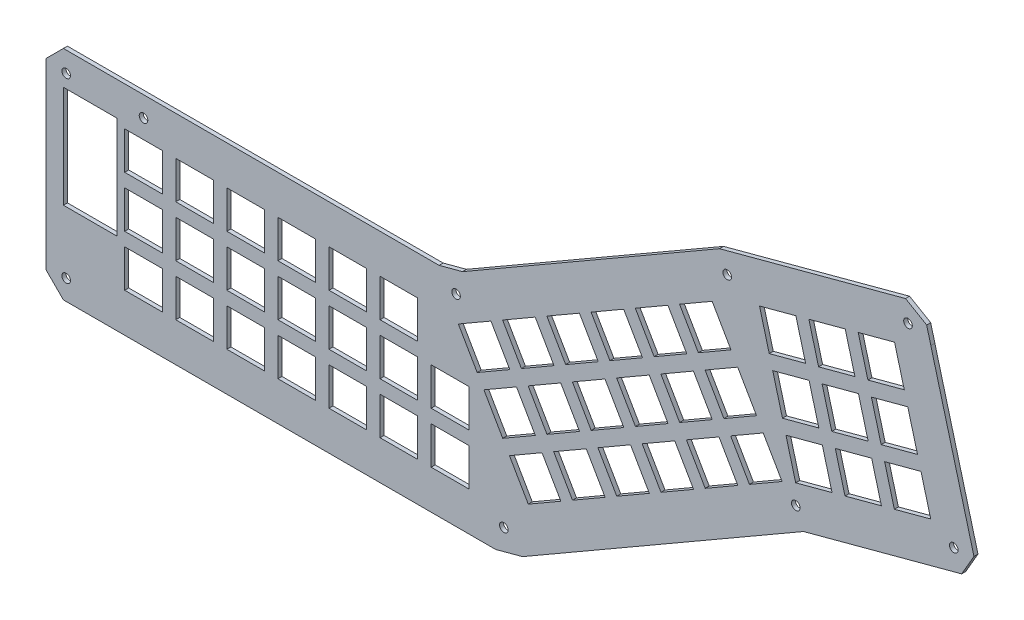
SolidWorks part; units mm, degrees
ref_plane "Plan de face" through (0, 0, 0) normal (0, 0, 1) x (1, 0, 0)
ref_plane "Plan de dessus" through (0, 0, 0) normal (0, 1, 0) x (1, 0, 0)
ref_plane "Plan de droite" through (0, 0, 0) normal (1, 0, 0) x (0, 0, -1)
sketch "Esquisse1" plane through (0, 0, 0) normal (0, 0, 1) x (1, 0, 0)
  line L0 (-73.9886, 18.0851) -> (-59.9886, 18.0851)
  line L1 (-73.9886, 37.0851) -> (-59.9886, 37.0851)
  line L2 (-73.9886, 37.0851) -> (-73.9886, 23.0851)
  line L3 (-73.9886, 23.0851) -> (-59.9886, 23.0851)
  line L4 (-59.9886, 37.0851) -> (-59.9886, 23.0851)
  line L5 (-73.9886, 18.0851) -> (-73.9886, 4.0851)
  line L6 (-73.9886, 4.0851) -> (-59.9886, 4.0851)
  line L7 (-59.9886, 18.0851) -> (-59.9886, 4.0851)
  line L8 (-73.9886, -0.9149) -> (-59.9886, -0.9149)
  line L9 (-73.9886, -0.9149) -> (-73.9886, -14.9149)
  line L10 (-73.9886, -14.9149) -> (-59.9886, -14.9149)
  line L11 (-59.9886, -0.9149) -> (-59.9886, -14.9149)
  line L12 (-73.9886, 37.0851) -> (-73.9886, 18.0851) construction
  line L13 (-54.9886, 18.0851) -> (-40.9886, 18.0851)
  line L14 (-54.9886, 37.0851) -> (-40.9886, 37.0851)
  line L15 (-54.9886, 37.0851) -> (-54.9886, 23.0851)
  line L16 (-54.9886, 23.0851) -> (-40.9886, 23.0851)
  line L17 (-40.9886, 37.0851) -> (-40.9886, 23.0851)
  line L18 (-54.9886, 18.0851) -> (-54.9886, 4.0851)
  line L19 (-54.9886, 4.0851) -> (-40.9886, 4.0851)
  line L20 (-40.9886, 18.0851) -> (-40.9886, 4.0851)
  line L21 (-54.9886, -0.9149) -> (-40.9886, -0.9149)
  line L22 (-54.9886, -0.9149) -> (-54.9886, -14.9149)
  line L23 (-54.9886, -14.9149) -> (-40.9886, -14.9149)
  line L24 (-40.9886, -0.9149) -> (-40.9886, -14.9149)
  line L25 (-54.9886, 37.0851) -> (-54.9886, 18.0851) construction
  line L26 (-35.9886, 18.0851) -> (-21.9886, 18.0851)
  line L27 (-35.9886, 37.0851) -> (-21.9886, 37.0851)
  line L28 (-35.9886, 37.0851) -> (-35.9886, 23.0851)
  line L29 (-35.9886, 23.0851) -> (-21.9886, 23.0851)
  line L30 (-21.9886, 37.0851) -> (-21.9886, 23.0851)
  line L31 (-35.9886, 18.0851) -> (-35.9886, 4.0851)
  line L32 (-35.9886, 4.0851) -> (-21.9886, 4.0851)
  line L33 (-21.9886, 18.0851) -> (-21.9886, 4.0851)
  line L34 (-35.9886, -0.9149) -> (-21.9886, -0.9149)
  line L35 (-35.9886, -0.9149) -> (-35.9886, -14.9149)
  line L36 (-35.9886, -14.9149) -> (-21.9886, -14.9149)
  line L37 (-21.9886, -0.9149) -> (-21.9886, -14.9149)
  line L38 (-35.9886, 37.0851) -> (-35.9886, 18.0851) construction
  line L39 (-16.9886, 18.0851) -> (-2.9886, 18.0851)
  line L40 (-16.9886, 37.0851) -> (-2.9886, 37.0851)
  line L41 (-16.9886, 37.0851) -> (-16.9886, 23.0851)
  line L42 (-16.9886, 23.0851) -> (-2.9886, 23.0851)
  line L43 (-2.9886, 37.0851) -> (-2.9886, 23.0851)
  line L44 (-16.9886, 18.0851) -> (-16.9886, 4.0851)
  line L45 (-16.9886, 4.0851) -> (-2.9886, 4.0851)
  line L46 (-2.9886, 18.0851) -> (-2.9886, 4.0851)
  line L47 (-16.9886, -0.9149) -> (-2.9886, -0.9149)
  line L48 (-16.9886, -0.9149) -> (-16.9886, -14.9149)
  line L49 (-16.9886, -14.9149) -> (-2.9886, -14.9149)
  line L50 (-2.9886, -0.9149) -> (-2.9886, -14.9149)
  line L51 (-16.9886, 37.0851) -> (-16.9886, 18.0851) construction
  line L52 (2.0114, 18.0851) -> (16.0114, 18.0851)
  line L53 (2.0114, 37.0851) -> (16.0114, 37.0851)
  line L54 (2.0114, 37.0851) -> (2.0114, 23.0851)
  line L55 (2.0114, 23.0851) -> (16.0114, 23.0851)
  line L56 (16.0114, 37.0851) -> (16.0114, 23.0851)
  line L57 (2.0114, 18.0851) -> (2.0114, 4.0851)
  line L58 (2.0114, 4.0851) -> (16.0114, 4.0851)
  line L59 (16.0114, 18.0851) -> (16.0114, 4.0851)
  line L60 (2.0114, -0.9149) -> (16.0114, -0.9149)
  line L61 (2.0114, -0.9149) -> (2.0114, -14.9149)
  line L62 (2.0114, -14.9149) -> (16.0114, -14.9149)
  line L63 (16.0114, -0.9149) -> (16.0114, -14.9149)
  line L64 (2.0114, 37.0851) -> (2.0114, 18.0851) construction
  line L65 (21.0114, 18.0851) -> (35.0114, 18.0851)
  line L66 (21.0114, 37.0851) -> (35.0114, 37.0851)
  line L67 (21.0114, 37.0851) -> (21.0114, 23.0851)
  line L68 (21.0114, 23.0851) -> (35.0114, 23.0851)
  line L69 (35.0114, 37.0851) -> (35.0114, 23.0851)
  line L70 (21.0114, 18.0851) -> (21.0114, 4.0851)
  line L71 (21.0114, 4.0851) -> (35.0114, 4.0851)
  line L72 (35.0114, 18.0851) -> (35.0114, 4.0851)
  line L73 (21.0114, -0.9149) -> (35.0114, -0.9149)
  line L74 (21.0114, -0.9149) -> (21.0114, -14.9149)
  line L75 (21.0114, -14.9149) -> (35.0114, -14.9149)
  line L76 (35.0114, -0.9149) -> (35.0114, -14.9149)
  line L77 (21.0114, 37.0851) -> (21.0114, 18.0851) construction
  line L78 (40.0114, 18.0851) -> (54.0114, 18.0851)
  line L79 (40.0114, 37.0851) -> (54.0114, 37.0851) construction
  line L80 (40.0114, 37.0851) -> (40.0114, 23.0851) construction
  line L81 (40.0114, 23.0851) -> (54.0114, 23.0851) construction
  line L82 (54.0114, 37.0851) -> (54.0114, 23.0851) construction
  line L83 (40.0114, 18.0851) -> (40.0114, 4.0851)
  line L84 (40.0114, 4.0851) -> (54.0114, 4.0851)
  line L85 (54.0114, 18.0851) -> (54.0114, 4.0851)
  line L86 (40.0114, -0.9149) -> (54.0114, -0.9149)
  line L87 (40.0114, -0.9149) -> (40.0114, -14.9149)
  line L88 (40.0114, -14.9149) -> (54.0114, -14.9149)
  line L89 (54.0114, -0.9149) -> (54.0114, -14.9149)
  line L90 (40.0114, 37.0851) -> (40.0114, 18.0851) construction
  line L91 (-73.9886, 18.0851) -> (-54.9886, 18.0851) construction
  line L92 (56.0114, 20.0851) -> (56.7532, 18.8002) construction
  line L93 (38.0114, 39.0851) -> (56.0114, 39.0851) construction
  line L94 (56.0114, 39.0851) -> (56.0114, 21.0851) construction
  line L95 (38.0114, 21.0851) -> (56.0114, 21.0851) construction
  line L96 (38.0114, 39.0851) -> (38.0114, 21.0851) construction
  line L97 (19.0114, 39.0851) -> (37.0114, 39.0851) construction
  line L98 (37.0114, 39.0851) -> (37.0114, 21.0851) construction
  line L99 (19.0114, 21.0851) -> (37.0114, 21.0851) construction
  line L100 (19.0114, 39.0851) -> (19.0114, 21.0851) construction
  line L101 (79.4363, 55.512) -> (88.4363, 39.9235) construction
  line L102 (88.4363, 39.9235) -> (72.8478, 30.9235) construction
  line L103 (63.8478, 46.512) -> (72.8478, 30.9235) construction
  line L104 (79.4363, 55.512) -> (63.8478, 46.512) construction
  line L105 (62.9818, 46.012) -> (71.9818, 30.4235) construction
  line L106 (71.9818, 30.4235) -> (56.3933, 21.4235) construction
  line L107 (47.3933, 37.012) -> (56.3933, 21.4235) construction
  line L108 (62.9818, 46.012) -> (47.3933, 37.012) construction
  line L109 (164.2542, 60.603) -> (148.6657, 51.603) construction
  line L110 (62.2497, 43.2799) -> (71.7497, 26.8254) construction
  line L111 (78.7042, 52.7799) -> (88.2042, 36.3254) construction
  line L112 (95.1587, 62.2799) -> (104.6587, 45.8254) construction
  line L113 (111.6132, 71.7799) -> (121.1132, 55.3254) construction
  line L114 (128.0677, 81.2799) -> (137.5677, 64.8254) construction
  line L115 (144.5221, 90.7799) -> (154.0221, 74.3254) construction
  line L116 (148.6657, 51.603) -> (157.6657, 36.0146) construction
  line L117 (69.1254, 3.371) -> (76.1254, -8.7534)
  line L118 (88.2497, -1.7534) -> (76.1254, -8.7534)
  line L119 (81.2497, 10.371) -> (88.2497, -1.7534)
  line L120 (81.2497, 10.371) -> (69.1254, 3.371)
  line L121 (59.6254, 19.8254) -> (66.6254, 7.7011)
  line L122 (78.7497, 14.7011) -> (66.6254, 7.7011)
  line L123 (71.7497, 26.8254) -> (78.7497, 14.7011)
  line L124 (50.1254, 36.2799) -> (57.1254, 24.1556)
  line L125 (69.2497, 31.1556) -> (57.1254, 24.1556)
  line L126 (62.2497, 43.2799) -> (69.2497, 31.1556)
  line L127 (62.2497, 43.2799) -> (50.1254, 36.2799)
  line L128 (71.7497, 26.8254) -> (59.6254, 19.8254)
  line L129 (85.5799, 12.871) -> (92.5799, 0.7466)
  line L130 (104.7042, 7.7466) -> (92.5799, 0.7466)
  line L131 (97.7042, 19.871) -> (104.7042, 7.7466)
  line L132 (97.7042, 19.871) -> (85.5799, 12.871)
  line L133 (76.0799, 29.3254) -> (83.0799, 17.2011)
  line L134 (95.2042, 24.2011) -> (83.0799, 17.2011)
  line L135 (88.2042, 36.3254) -> (95.2042, 24.2011)
  line L136 (66.5799, 45.7799) -> (73.5799, 33.6556)
  line L137 (85.7042, 40.6556) -> (73.5799, 33.6556)
  line L138 (78.7042, 52.7799) -> (85.7042, 40.6556)
  line L139 (78.7042, 52.7799) -> (66.5799, 45.7799)
  line L140 (88.2042, 36.3254) -> (76.0799, 29.3254)
  line L141 (102.0343, 22.371) -> (109.0343, 10.2466)
  line L142 (121.1587, 17.2466) -> (109.0343, 10.2466)
  line L143 (114.1587, 29.371) -> (121.1587, 17.2466)
  line L144 (114.1587, 29.371) -> (102.0343, 22.371)
  line L145 (92.5343, 38.8254) -> (99.5343, 26.7011)
  line L146 (111.6587, 33.7011) -> (99.5343, 26.7011)
  line L147 (104.6587, 45.8254) -> (111.6587, 33.7011)
  line L148 (83.0343, 55.2799) -> (90.0343, 43.1556)
  line L149 (102.1587, 50.1556) -> (90.0343, 43.1556)
  line L150 (95.1587, 62.2799) -> (102.1587, 50.1556)
  line L151 (95.1587, 62.2799) -> (83.0343, 55.2799)
  line L152 (104.6587, 45.8254) -> (92.5343, 38.8254)
  line L153 (118.4888, 31.871) -> (125.4888, 19.7466)
  line L154 (137.6132, 26.7466) -> (125.4888, 19.7466)
  line L155 (130.6132, 38.871) -> (137.6132, 26.7466)
  line L156 (130.6132, 38.871) -> (118.4888, 31.871)
  line L157 (108.9888, 48.3254) -> (115.9888, 36.2011)
  line L158 (128.1132, 43.2011) -> (115.9888, 36.2011)
  line L159 (121.1132, 55.3254) -> (128.1132, 43.2011)
  line L160 (99.4888, 64.7799) -> (106.4888, 52.6556)
  line L161 (118.6132, 59.6556) -> (106.4888, 52.6556)
  line L162 (111.6132, 71.7799) -> (118.6132, 59.6556)
  line L163 (111.6132, 71.7799) -> (99.4888, 64.7799)
  line L164 (121.1132, 55.3254) -> (108.9888, 48.3254)
  line L165 (134.9433, 41.371) -> (141.9433, 29.2466)
  line L166 (154.0677, 36.2466) -> (141.9433, 29.2466)
  line L167 (147.0677, 48.371) -> (154.0677, 36.2466)
  line L168 (147.0677, 48.371) -> (134.9433, 41.371)
  line L169 (125.4433, 57.8254) -> (132.4433, 45.7011)
  line L170 (144.5677, 52.7011) -> (132.4433, 45.7011)
  line L171 (137.5677, 64.8254) -> (144.5677, 52.7011)
  line L172 (115.9433, 74.2799) -> (122.9433, 62.1556)
  line L173 (135.0677, 69.1556) -> (122.9433, 62.1556)
  line L174 (128.0677, 81.2799) -> (135.0677, 69.1556)
  line L175 (128.0677, 81.2799) -> (115.9433, 74.2799)
  line L176 (137.5677, 64.8254) -> (125.4433, 57.8254)
  line L177 (151.3978, 50.871) -> (158.3978, 38.7466)
  line L178 (170.5221, 45.7466) -> (158.3978, 38.7466)
  line L179 (163.5221, 57.871) -> (170.5221, 45.7466)
  line L180 (163.5221, 57.871) -> (151.3978, 50.871)
  line L181 (141.8978, 67.3254) -> (148.8978, 55.2011)
  line L182 (161.0221, 62.2011) -> (148.8978, 55.2011)
  line L183 (154.0221, 74.3254) -> (161.0221, 62.2011)
  line L184 (132.3978, 83.7799) -> (139.3978, 71.6556)
  line L185 (151.5221, 78.6556) -> (139.3978, 71.6556)
  line L186 (144.5221, 90.7799) -> (151.5221, 78.6556)
  line L187 (144.5221, 90.7799) -> (132.3978, 83.7799)
  line L188 (154.0221, 74.3254) -> (141.8978, 67.3254)
  line L189 (173.2542, 45.0146) -> (157.6657, 36.0146) construction
  line L190 (164.2542, 60.603) -> (173.2542, 45.0146) construction
  line L191 (178.3169, 34.0986) -> (169.0534, 56.4627) construction
  line L192 (169.5193, 62.7839) -> (174.1781, 45.3972) construction
  line L193 (174.1781, 45.3972) -> (191.5647, 50.056) construction
  line L194 (186.906, 67.4426) -> (191.5647, 50.056) construction
  line L195 (162.1337, 98.0749) -> (167.0513, 79.7223) construction
  line L196 (169.5193, 62.7839) -> (186.906, 67.4426) construction
  line L197 (167.0513, 79.7223) -> (180.5742, 83.3457)
  line L198 (162.1337, 98.0749) -> (175.6567, 101.6983)
  line L199 (162.1337, 98.0749) -> (165.7572, 84.5519)
  line L200 (165.7572, 84.5519) -> (179.2801, 88.1754)
  line L201 (175.6567, 101.6983) -> (179.2801, 88.1754)
  line L202 (167.0513, 79.7223) -> (170.6747, 66.1993)
  line L203 (170.6747, 66.1993) -> (184.1977, 69.8228)
  line L204 (180.5742, 83.3457) -> (184.1977, 69.8228)
  line L205 (171.9688, 61.3697) -> (185.4918, 64.9932)
  line L206 (171.9688, 61.3697) -> (175.5923, 47.8467)
  line L207 (175.5923, 47.8467) -> (189.1152, 51.4702)
  line L208 (185.4918, 64.9932) -> (189.1152, 51.4702)
  line L209 (185.4038, 84.6398) -> (198.9268, 88.2633)
  line L210 (180.4863, 102.9924) -> (194.0092, 106.6159)
  line L211 (180.4863, 102.9924) -> (184.1097, 89.4695)
  line L212 (184.1097, 89.4695) -> (197.6327, 93.0929)
  line L213 (194.0092, 106.6159) -> (197.6327, 93.0929)
  line L214 (185.4038, 84.6398) -> (189.0273, 71.1169)
  line L215 (189.0273, 71.1169) -> (202.5503, 74.7403)
  line L216 (198.9268, 88.2633) -> (202.5503, 74.7403)
  line L217 (190.3214, 66.2873) -> (203.8444, 69.9107)
  line L218 (190.3214, 66.2873) -> (193.9449, 52.7643)
  line L219 (193.9449, 52.7643) -> (207.4678, 56.3878)
  line L220 (203.8444, 69.9107) -> (207.4678, 56.3878)
  line L221 (187.8719, 67.7015) -> (192.5307, 50.3148) construction
  line L222 (192.5307, 50.3148) -> (209.9173, 54.9735) construction
  line L223 (205.2586, 72.3602) -> (209.9173, 54.9735) construction
  line L224 (180.4863, 102.9924) -> (185.4038, 84.6398) construction
  line L225 (187.8719, 67.7015) -> (205.2586, 72.3602) construction
  line L226 (203.7564, 89.5574) -> (217.2794, 93.1809)
  line L227 (198.8389, 107.91) -> (212.3618, 111.5335)
  line L228 (198.8389, 107.91) -> (202.4623, 94.387)
  line L229 (202.4623, 94.387) -> (215.9853, 98.0105)
  line L230 (212.3618, 111.5335) -> (215.9853, 98.0105)
  line L231 (203.7564, 89.5574) -> (207.3799, 76.0344)
  line L232 (207.3799, 76.0344) -> (220.9029, 79.6579)
  line L233 (217.2794, 93.1809) -> (220.9029, 79.6579)
  line L234 (208.674, 71.2048) -> (222.197, 74.8283)
  line L235 (208.674, 71.2048) -> (212.2975, 57.6819)
  line L236 (212.2975, 57.6819) -> (225.8204, 61.3053)
  line L237 (222.197, 74.8283) -> (225.8204, 61.3053)
  line L238 (206.2245, 72.619) -> (210.8833, 55.2324) construction
  line L239 (210.8833, 55.2324) -> (228.2699, 59.8911) construction
  line L240 (223.6112, 77.2778) -> (228.2699, 59.8911) construction
  line L241 (198.8389, 107.91) -> (203.7564, 89.5574) construction
  line L242 (206.2245, 72.619) -> (223.6112, 77.2778) construction
  line L243 (167.0513, 79.7223) -> (185.4038, 84.6398) construction
  line L244 (38.0114, 20.0851) -> (56.0114, 20.0851) construction
  line L245 (56.0114, 20.0851) -> (56.0114, 2.0851) construction
  line L246 (38.0114, 2.0851) -> (56.0114, 2.0851) construction
  line L247 (38.0114, 20.0851) -> (38.0114, 2.0851) construction
  line L248 (72.4818, 29.5575) -> (56.8933, 20.5575) construction
  line L249 (56.8933, 20.5575) -> (65.8933, 4.969) construction
  line L250 (81.4818, 13.969) -> (65.8933, 4.969) construction
  line L251 (72.4818, 29.5575) -> (81.4818, 13.969) construction
  line L252 (56.8933, 20.5575) -> (57.6111, 19.3142) construction
  line L253 (164.6018, 81.1365) -> (169.2605, 63.7498) construction
  line L254 (169.2605, 63.7498) -> (186.6472, 68.4086) construction
  line L255 (181.9884, 85.7952) -> (186.6472, 68.4086) construction
  line L256 (164.6018, 81.1365) -> (181.9884, 85.7952) construction
  line L257 (154.7542, 77.0575) -> (163.7542, 61.469) construction
  line L258 (163.7542, 61.469) -> (148.1657, 52.469) construction
  line L259 (139.1657, 68.0575) -> (148.1657, 52.469) construction
  line L260 (154.7542, 77.0575) -> (139.1657, 68.0575) construction
  line L261 (196.3894, 109.3242) -> (213.776, 113.983) construction
  line L262 (-94.7538, 35.7952) -> (-76.7538, 35.7952) construction
  line L263 (-94.7538, 35.7952) -> (-94.7538, 2.7952) construction
  line L264 (-94.7538, 2.7952) -> (-76.7538, 2.7952) construction
  line L265 (-76.7538, 35.7952) -> (-76.7538, 2.7952) construction
  line L266 (213.776, 113.983) -> (218.4348, 96.5963) construction
  line L267 (201.0481, 91.9375) -> (218.4348, 96.5963) construction
  line L268 (196.3894, 109.3242) -> (201.0481, 91.9375) construction
  line L269 (-75.9886, -16.9149) -> (-57.9886, -16.9149) construction
  line L270 (-57.9886, 1.0851) -> (-57.9886, -16.9149) construction
  line L271 (-75.9886, 1.0851) -> (-57.9886, 1.0851) construction
  line L272 (-75.9886, 1.0851) -> (-75.9886, -16.9149) construction
  line L273 (38.0114, -16.9149) -> (56.0114, -16.9149) construction
  line L274 (56.0114, 1.0851) -> (56.0114, -16.9149) construction
  line L275 (38.0114, 1.0851) -> (56.0114, 1.0851) construction
  line L276 (38.0114, 1.0851) -> (38.0114, -16.9149) construction
  line L277 (-75.9886, 39.0851) -> (-57.9886, 39.0851) construction
  line L278 (-57.9886, 39.0851) -> (-57.9886, 21.0851) construction
  line L279 (-75.9886, 21.0851) -> (-57.9886, 21.0851) construction
  line L280 (-75.9886, 39.0851) -> (-75.9886, 21.0851) construction
  line L281 (145.2542, 93.512) -> (129.6657, 84.512) construction
  line L282 (129.6657, 84.512) -> (138.6657, 68.9235) construction
  line L283 (154.2542, 77.9235) -> (138.6657, 68.9235) construction
  line L284 (145.2542, 93.512) -> (154.2542, 77.9235) construction
  line L285 (223.4353, 116.5711) -> (228.0941, 99.1845) construction
  line L286 (148.2159, 106.7689) -> (211.1879, 123.6422) construction
  line L287 (177.5508, 35.9482) -> (235.6877, 51.5259) construction
  line L288 (177.5508, 35.9482) -> (72.9989, -24.4149) construction
  line L289 (-95.7538, -26.9149) -> (63.6687, -26.9149) construction
  line L290 (-100.7538, 35.7952) -> (-100.7538, -21.9149) construction
  line L291 (-75.9886, 49.0851) -> (43.3046, 49.0851) construction
  line L292 (148.2159, 106.7689) -> (52.6347, 51.5851) construction
  line L293 (-75.9886, 49.0851) -> (-57.9886, 49.0851) construction
  line L294 (140.2542, 102.1722) -> (124.6657, 93.1722) construction
  line L295 (193.8012, 118.9835) -> (211.1879, 123.6422) construction
  line L296 (213.4714, 45.5731) -> (230.8581, 50.2318) construction
  line L297 (38.0114, -26.9149) -> (38.0114, -85.4624) construction
  line L298 (178.2542, 36.3543) -> (162.6657, 27.3543) construction
  line L299 (38.0114, -26.9149) -> (56.0114, -26.9149) construction
  line L300 (-100.7538, 2.7952) -> (-100.7538, -38.0419) construction
  line L301 (-100.7538, 35.7952) -> (-100.7538, 2.7952) construction
  line L302 (-75.9886, 49.0851) -> (-95.7538, 49.0851) construction
  line L303 (-100.7538, 44.0851) -> (-100.7538, 35.7952) construction
  line L304 (211.1879, 123.6422) -> (216.0732, 124.9512) construction
  line L305 (222.1691, 121.4083) -> (223.4353, 116.5711) construction
  line L306 (228.0941, 99.1845) -> (239.2233, 57.6497) construction
  line L307 (216.0732, 124.9512) -> (222.1691, 121.4083) construction
  line L308 (235.6877, 51.5259) -> (239.2233, 57.6497) construction
  line L309 (63.6687, -26.9149) -> (72.9989, -24.4149) construction
  line L310 (52.6347, 51.5851) -> (43.3046, 49.0851) construction
  line L311 (-95.7538, 49.0851) -> (-100.7538, 44.0851) construction
  line L312 (-100.7538, -21.9149) -> (-95.7538, -26.9149) construction
  line L313 (-95.7538, 49.0851) -> (-95.7538, 44.0851) construction
  line L314 (-95.7538, 44.0851) -> (-100.7538, 44.0851) construction
  line L315 (-95.7538, -26.9149) -> (-95.7538, -21.9149) construction
  line L316 (68.3338, -25.6649) -> (67.0397, -20.8353) construction
  line L317 (47.9697, 50.3351) -> (49.2637, 45.5055) construction
  line L318 (177.5508, 35.9482) -> (175.6374, 40.5676) construction
  line L319 (148.2159, 106.7689) -> (150.1293, 102.1495) construction
  line L320 (239.2233, 57.6497) -> (234.3936, 56.3556) construction
  line L321 (216.0732, 124.9512) -> (217.3634, 120.1206) construction
  line L322 (-66.9886, 37.0851) -> (-66.9886, 49.0851) construction
  line L323 (-76.7538, 35.7952) -> (-96.7538, 35.7952) construction
  line L324 (-95.7538, 44.0851) -> (-65.1374, 44.0851) construction
  line L325 (-76.7538, 39.0851) -> (-96.7538, 39.0851)
  line L326 (-76.7538, 39.0851) -> (-76.7538, 1.0851)
  line L327 (-76.7538, 1.0851) -> (-96.7538, 1.0851)
  line L328 (-96.7538, 39.0851) -> (-96.7538, 1.0851)
  line L329 (-75.9886, 50.5851) -> (43.1071, 50.5851) construction
  line L330 (52.0557, 52.9829) -> (43.1071, 50.5851) construction
  line L331 (147.6369, 108.1667) -> (52.0557, 52.9829) construction
  line L332 (147.6369, 108.1667) -> (210.7996, 125.0911) construction
  line L333 (210.7996, 125.0911) -> (216.2876, 126.5616) construction
  line L334 (216.2876, 126.5616) -> (223.4622, 122.3917) construction
  line L335 (223.4622, 122.3917) -> (224.8853, 116.9552) construction
  line L336 (224.8853, 116.9552) -> (229.5429, 99.5727) construction
  line L337 (229.5429, 99.5727) -> (240.833, 57.4377) construction
  line L338 (236.6761, 50.2379) -> (240.833, 57.4377) construction
  line L339 (178.1298, 34.5504) -> (236.6761, 50.2379) construction
  line L340 (178.1298, 34.5504) -> (73.5778, -25.8127) construction
  line L341 (63.8662, -28.4149) -> (73.5778, -25.8127) construction
  line L342 (-96.3751, -28.4149) -> (63.8662, -28.4149) construction
  line L343 (-102.2538, -22.5362) -> (-96.3751, -28.4149) construction
  line L344 (-102.2538, 35.7952) -> (-102.2538, -22.5362) construction
  line L345 (-102.2538, 44.7064) -> (-102.2538, 35.7952) construction
  line L346 (-96.3751, 50.5851) -> (-102.2538, 44.7064) construction
  line L347 (-75.9886, 50.5851) -> (-96.3751, 50.5851) construction
  line L348 (-75.9886, 52.5851) -> (42.8438, 52.5851) construction
  line L349 (51.2838, 54.8466) -> (42.8438, 52.5851) construction
  line L350 (146.8649, 110.0304) -> (51.2838, 54.8466) construction
  line L351 (146.8649, 110.0304) -> (210.282, 127.023) construction
  line L352 (210.282, 127.023) -> (216.5734, 128.7087) construction
  line L353 (216.5734, 128.7087) -> (225.1863, 123.7029) construction
  line L354 (225.1863, 123.7029) -> (226.8187, 117.4673) construction
  line L355 (226.8187, 117.4673) -> (231.4748, 100.0903) construction
  line L356 (231.4748, 100.0903) -> (242.9792, 57.1552) construction
  line L357 (237.994, 48.5204) -> (242.9792, 57.1552) construction
  line L358 (178.9017, 32.6867) -> (237.994, 48.5204) construction
  line L359 (178.9017, 32.6867) -> (74.3498, -27.6764) construction
  line L360 (64.1295, -30.4149) -> (74.3498, -27.6764) construction
  line L361 (-97.2035, -30.4149) -> (64.1295, -30.4149) construction
  line L362 (-104.2538, -23.3646) -> (-97.2035, -30.4149) construction
  line L363 (-104.2538, 35.7952) -> (-104.2538, -23.3646) construction
  line L364 (-104.2538, 45.5349) -> (-104.2538, 35.7952) construction
  line L365 (-97.2035, 52.5851) -> (-104.2538, 45.5349) construction
  line L366 (-75.9886, 52.5851) -> (-97.2035, 52.5851) construction
  line L367 (-75.9886, 51.5851) -> (42.9755, 51.5851)
  line L368 (51.6698, 53.9147) -> (42.9755, 51.5851)
  line L369 (147.2509, 109.0986) -> (51.6698, 53.9147)
  line L370 (147.2509, 109.0986) -> (210.5408, 126.057)
  line L371 (210.5408, 126.057) -> (216.4305, 127.6352)
  line L372 (216.4305, 127.6352) -> (224.3243, 123.0473)
  line L373 (224.3243, 123.0473) -> (225.852, 117.2112)
  line L374 (225.852, 117.2112) -> (230.5089, 99.8315)
  line L375 (230.5089, 99.8315) -> (241.9061, 57.2965)
  line L376 (237.335, 49.3791) -> (241.9061, 57.2965)
  line L377 (178.5158, 33.6186) -> (237.335, 49.3791)
  line L378 (178.5158, 33.6186) -> (73.9638, -26.7445)
  line L379 (63.9979, -29.4149) -> (73.9638, -26.7445)
  line L380 (-96.7893, -29.4149) -> (63.9979, -29.4149)
  line L381 (-103.2538, -22.9504) -> (-96.7893, -29.4149)
  line L382 (-103.2538, 35.7952) -> (-103.2538, -22.9504)
  line L383 (-103.2538, 45.1206) -> (-103.2538, 35.7952)
  line L384 (-96.7893, 51.5851) -> (-103.2538, 45.1206)
  line L385 (-75.9886, 51.5851) -> (-96.7893, 51.5851)
  circle A0 centre (-95.7538, 44.0851) radius 1.5 construction
  circle A1 centre (-95.7538, -21.9149) radius 1.5 construction
  circle A2 centre (67.0397, -20.8353) radius 1.5 construction
  circle A3 centre (49.2637, 45.5055) radius 1.5 construction
  circle A4 centre (175.6374, 40.5676) radius 1.5 construction
  circle A5 centre (150.1293, 102.1495) radius 1.5 construction
  circle A6 centre (234.3936, 56.3556) radius 1.5 construction
  circle A7 centre (217.3634, 120.1206) radius 1.5 construction
  circle A8 centre (-66.9886, 44.0851) radius 1.5 construction
  circle A9 centre (-95.7538, 44.0851) radius 1.6
  circle A10 centre (-66.9886, 44.0851) radius 1.6
  circle A11 centre (-95.7538, -21.9149) radius 1.6
  circle A12 centre (67.0397, -20.8353) radius 1.6
  circle A13 centre (49.2637, 45.5055) radius 1.6
  circle A14 centre (175.6374, 40.5676) radius 1.6
  circle A15 centre (150.1293, 102.1495) radius 1.6
  circle A16 centre (217.3634, 120.1206) radius 1.6
  circle A17 centre (234.3936, 56.3556) radius 1.6
  point P304 (48.3046, 49.0851)
  point P305 (240.5174, 52.82)
  point P308 (68.6687, -26.9149)
  point P309 (-100.7538, -26.9149)
  point P311 (-100.7538, 49.0851)
  point P312 (220.9029, 126.2453)
  dimension "D32" = 3
  dimension "D33" = 5
  dimension "D40" = 5
  dimension "D41" = 5
  dimension "D42" = 5
  dimension "D43" = 5
  dimension "D44" = 20
  dimension "D45" = 1.5
  dimension "D49" = 0.1
  dimension "D1" = 14
  dimension "D2" = 14
  dimension "D4" = 19
  dimension "D6" = 19
  dimension "D7" = 30
  dimension "D10" = 1
  dimension "D11" = 2
  dimension "D13" = 0.5
  dimension "D15" = 2
  dimension "D12" = 7.5
  dimension "D14" = 19
  dimension "D18" = 2
  dimension "D20" = 18
  dimension "D21" = 33
  dimension "D22" = 2
  dimension "D8" = 2
  dimension "D9" = 2
  dimension "D16" = 2
  dimension "D19" = 2
  dimension "D23" = 2
  dimension "D24" = 10
  dimension "D25" = 10
  dimension "D26" = 10
  dimension "D27" = 10
  dimension "D28" = 10
  dimension "D29" = 6
  dimension "D30" = 10
  dimension "D31" = 10
  dimension "D46" = 2
  dimension "D47" = 1
  dimension "D48" = 0.1
  dimension "D3" = 3
  dimension "D5" = 7
  dimension "D17" = 3
extrude "Boss.-Extru.1" add sketch "Esquisse1" along normal blind 1.5
